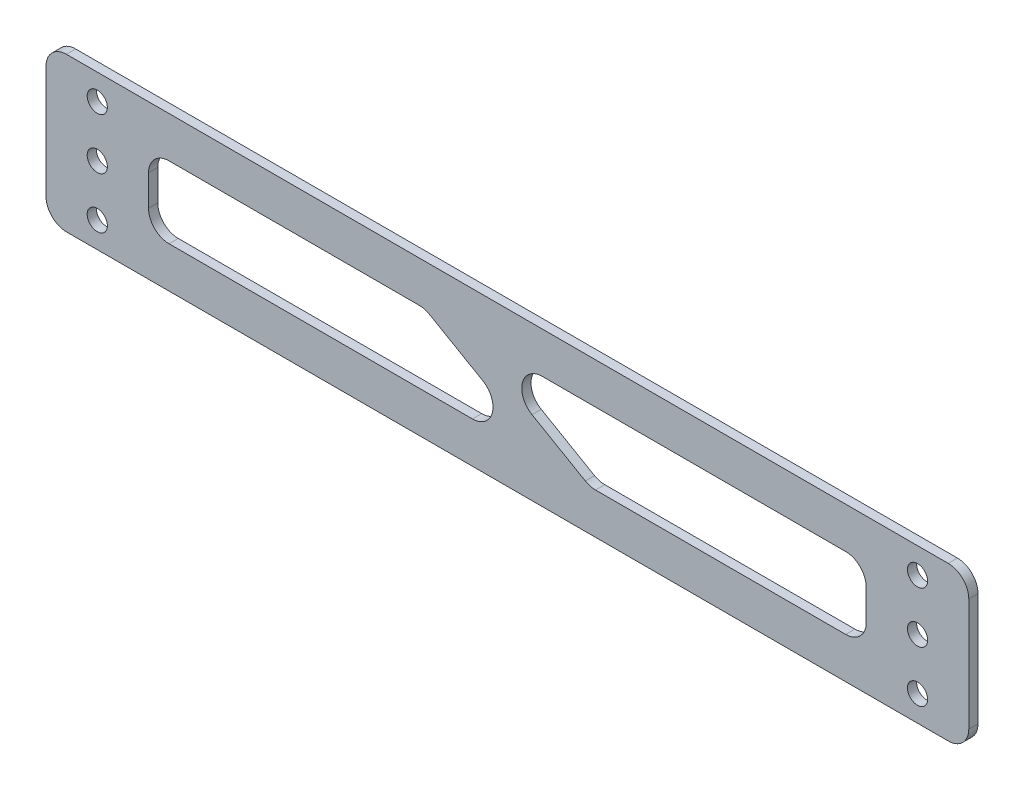
SolidWorks part; units mm, degrees
material "6061-T6 (SS)"
ref_plane "Front Plane" through (0, 0, 0) normal (0, 0, 1) x (1, 0, 0)
ref_plane "Top Plane" through (0, 0, 0) normal (0, 1, 0) x (1, 0, 0)
ref_plane "Right Plane" through (0, 0, 0) normal (1, 0, 0) x (0, 0, -1)
sketch "Sketch1" plane through (0, 0, 0) normal (0, 0, 1) x (1, 0, 0)
  line L1 (-12.7, 774.7) -> (49987.3, 774.7) construction
  line L2 (-7.62, 368.3) -> (210.82, 368.3) construction
  line L3 (-12.7, 1181.1) -> (-12.7, 368.3) construction
  line L4 (-7.62, 755.65) -> (210.82, 755.65)
  line L5 (-12.7, 760.73) -> (-12.7, 788.67)
  line L6 (-7.62, 793.75) -> (210.82, 793.75)
  line L7 (215.9, 760.73) -> (215.9, 788.67)
  line L8 (215.9, 1181.1) -> (215.9, 368.3) construction
  line L9 (17.78, 783.59) -> (79.7609, 783.59)
  line L10 (12.7, 1181.1) -> (12.7, 368.3) construction
  line L11 (190.5, 1181.1) -> (190.5, 368.3) construction
  line L12 (190.5, 778.51) -> (190.5, 770.89)
  line L13 (185.42, 765.81) -> (123.4391, 765.81)
  line L14 (12.7, 770.89) -> (12.7, 778.51)
  line L15 (82.3009, 782.9094) -> (95.4991, 775.2894)
  line L16 (107.7009, 774.1106) -> (120.8991, 766.4906)
  line L17 (81.1221, 783.59) -> (81.1221, -49216.41) construction
  line L18 (122.0779, 765.81) -> (122.0779, 50765.81) construction
  line L19 (101.6, 765.81) -> (101.6, 50765.81) construction
  line L20 (110.2409, 783.59) -> (185.42, 783.59)
  line L21 (92.9591, 765.81) -> (17.78, 765.81)
  arc A0 (210.82, 793.75) -> (215.9, 788.67) centre (210.82, 788.67) cw
  arc A1 (210.82, 755.65) -> (215.9, 760.73) centre (210.82, 760.73) ccw
  arc A2 (-12.7, 788.67) -> (-7.62, 793.75) centre (-7.62, 788.67) cw
  arc A3 (-7.62, 755.65) -> (-12.7, 760.73) centre (-7.62, 760.73) cw
  circle A4 centre (0, 762) radius 2.5
  circle A5 centre (0, 774.7) radius 2.5
  circle A6 centre (0, 787.4) radius 2.5
  circle A7 centre (203.2, 762) radius 2.5
  circle A8 centre (203.2, 774.7) radius 2.5
  circle A9 centre (203.2, 787.4) radius 2.5
  arc A10 (185.42, 783.59) -> (190.5, 778.51) centre (185.42, 778.51) cw
  arc A11 (190.5, 770.89) -> (185.42, 765.81) centre (185.42, 770.89) cw
  arc A12 (17.78, 765.81) -> (12.7, 770.89) centre (17.78, 770.89) cw
  arc A13 (17.78, 783.59) -> (12.7, 778.51) centre (17.78, 778.51) ccw
  arc A14 (120.8991, 766.4906) -> (123.4391, 765.81) centre (123.4391, 770.89) ccw
  arc A15 (107.7009, 774.1106) -> (110.2409, 783.59) centre (110.2409, 778.51) cw
  arc A16 (82.3009, 782.9094) -> (79.7609, 783.59) centre (79.7609, 778.51) ccw
  arc A17 (95.4991, 775.2894) -> (92.9591, 765.81) centre (92.9591, 770.89) cw
  point P14 (215.9, 793.75)
  point P17 (215.9, 755.65)
  point P22 (-12.7, 755.65)
  point P55 (190.5, 783.59)
  point P58 (190.5, 765.81)
  point P61 (12.7, 765.81)
  point P64 (12.7, 783.59)
  point P73 (122.0779, 765.81)
  point P76 (91.2821, 783.59)
  point P79 (81.1221, 783.59)
  point P82 (111.9179, 765.81)
  dimension "D4" = 5.08
  dimension "D7" = 5.08
  dimension "D12" = 5.08
  dimension "D1" = 406.4
  dimension "D2" = 38.1
  dimension "D3" = 19.05
  dimension "D5" = 10.16
  dimension "D6" = 10.16
  dimension "D8" = 5.08
  dimension "D9" = 30
  dimension "D10" = 20.4779
  dimension "D11" = 88.9
extrude "Boss-Extrude1" add sketch "Sketch1" along normal blind 2.286
sketch "Sketch2" [suppressed] plane through (0, 0, 0) normal (0, 0, 1) x (1, 0, 0)
  circle A0 centre (27.1191, 775.0388) radius 2.54
  circle A1 centre (68.5634, 775.0388) radius 2.54
  circle A2 centre (133.0475, 775.0388) radius 2.54
  circle A3 centre (171.352, 775.0388) radius 2.54
  dimension "D1" = 5.08
